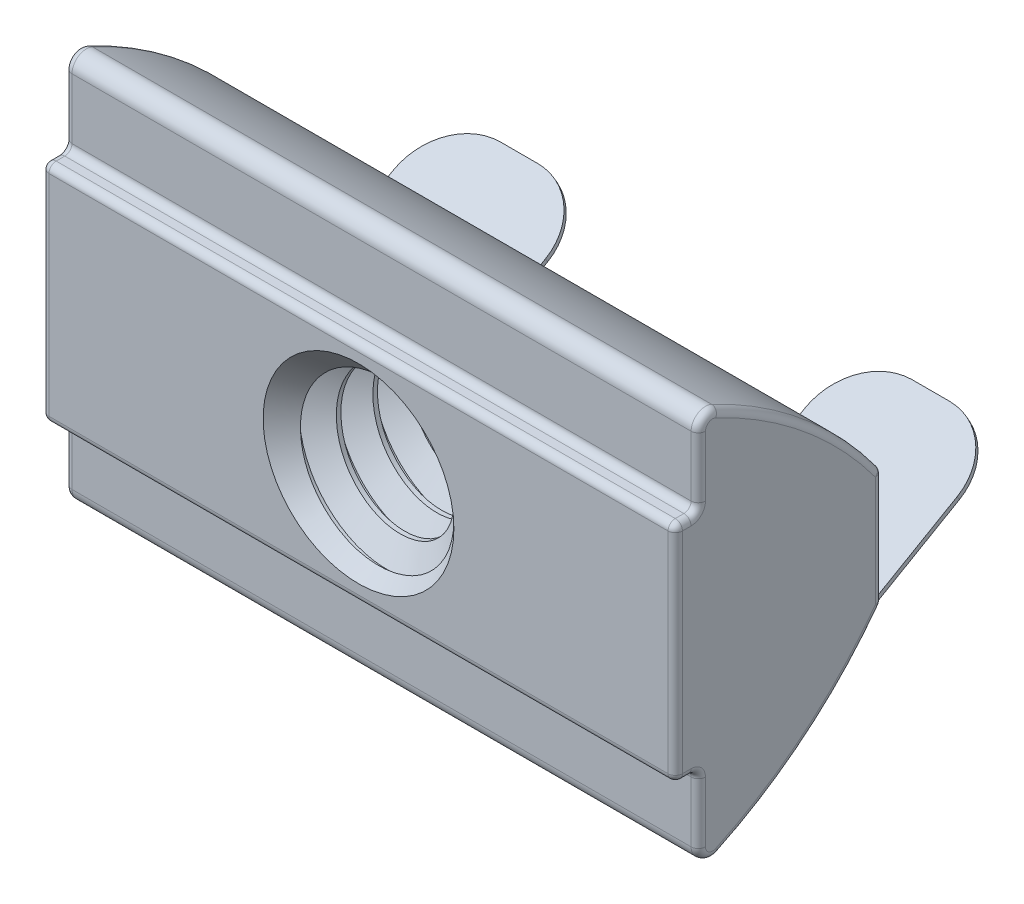
SolidWorks part; units mm, degrees
ref_plane "Front Plane" through (0, 0, 0) normal (0, 0, 1) x (1, 0, 0)
ref_plane "Top Plane" through (0, 0, 0) normal (0, 1, 0) x (1, 0, 0)
ref_plane "Right Plane" through (0, 0, 0) normal (1, 0, 0) x (0, 0, -1)
sketch "Sketch1" plane through (0, 0, 0) normal (0, 0, 1) x (1, 0, 0)
  line L1 (-11, 6.75) -> (11, 6.75)
  line L2 (-11, 6.75) -> (-11, -6.75)
  line L3 (-11, -6.75) -> (11, -6.75)
  line L4 (11, 6.75) -> (11, -6.75)
  circle A0 centre (0, 0) radius 3.175
  point P4 (0, 6.75)
  point P5 (0, 0)
  point P6 (-11, 0)
  point P11 (0, 3.175)
  dimension "Thread Diameter" = 6.35
  dimension "Length" = 22
  dimension "Width" = 13.5
sketch "Sketch2" plane through (0, 0, 0) normal (1, 0, 0) x (0, 0, -1)
  line L0 (-3.6, -3.9) -> (-3.6, 3.9)
  line L1 (-3.6, 3.9) -> (-2.8, 3.9)
  line L4 (-3.6, -3.9) -> (-2.8, -3.9)
  line L8 (-3.6, 0) -> (3.6, 0)
  line L13 (-4.7906, 3.3125) -> (-4.1556, 2.2126)
  line L14 (-4.1556, 2.2126) -> (-3.5206, 3.3125)
  line L15 (-3.5206, 3.3125) -> (-4.7906, 3.3125)
  line L16 (-4.1556, 3.3125) -> (-4.1556, 3.175)
  line L17 (-4.1556, 2.2126) -> (-4.1556, 2.3501)
  line L18 (-4.7113, 3.175) -> (-3.6, 3.175)
  line L19 (-4.7509, 3.2437) -> (-3.5603, 3.2437)
  line L20 (-4.235, 2.3501) -> (-4.0763, 2.3501)
  point P12 (0, 0)
  point P30 (9.2, 0)
  point P39 (-4.1556, 3.175)
  point P42 (-4.1556, 3.2437)
  point P45 (-4.1556, 2.3501)
  dimension "Thickness" = 7.2
  dimension "D2" = 7.8
  dimension "D3" = 0.8
  dimension "Thread Pitch" = 1.27
  dimension "D12" = 0.1588
  dimension "Spring Length" = 12
sketch "Sketch4" plane through (0, 0, 0) normal (1, 0, 0) x (0, 0, -1)
  line L3 (-3.6, -3.9) -> (-2.8, -3.9) construction
  line L4 (-3.6, -3.9) -> (-3.6, 3.9) construction
  line L5 (-3.6, 3.9) -> (-2.8, 3.9) construction
  line L11 (-3.6, -3.9) -> (-2.8, -3.9)
  line L12 (-3.6, -3.9) -> (-3.6, 3.9)
  line L13 (-3.6, 3.9) -> (-2.8, 3.9)
  line L16 (-2.8, 3.9) -> (-2.8, 6.25)
  line L17 (-2.8, -3.9) -> (-2.8, -6.25)
  line L18 (3.6, 2) -> (3.6, -2)
  arc A8 (-2.0859, 6.7019) -> (3.6, 2) centre (-8.5084, -6.8537) cw
  arc A9 (-2.0859, -6.7019) -> (3.6, -2) centre (-8.5084, 6.8537) ccw
  arc A10 (-2.0859, -6.7019) -> (-2.8, -6.25) centre (-2.3, -6.25) cw
  arc A11 (-2.0859, 6.7019) -> (-2.8, 6.25) centre (-2.3, 6.25) ccw
  point P14 (-2.3, 6.75)
  dimension "D1" = 0.5
  dimension "D2" = 15
  dimension "D3" = 4
extrude "Boss-Extrude1" add sketch "Sketch4" against normal up to vertex (11 mm away) and the other way up to vertex (11 mm away) up to point (-11, 6.75, 0) other way up to point (11, 6.75, 0)
sketch "Sketch6" plane through (0, 0, 3.6) normal (0, 0, 1) x (1, 0, 0)
  circle A0 centre (0, 0) radius 3.175 construction
  circle A1 centre (0, 0) radius 3.175
extrude "Cut-Extrude2" cut sketch "Sketch6" against normal through all
sketch "Sketch7" plane through (0, 0, 0) normal (1, 0, 0) x (0, 0, -1)
  line L8 (-2.0859, -6.7588) -> (9.125, -0.2862)
  line L9 (9.125, -0.2862) -> (9.2, -0.4161)
  line L10 (9.2, -0.4161) -> (-2.0109, -6.8887)
  line L11 (-2.0109, -6.8887) -> (-2.0859, -6.7588)
  line L12 (-2.8, -3.9) -> (-2.8, -6.25) construction
  arc A4 (-2.0859, -6.7019) -> (3.6, -2) centre (-8.5084, 6.8537) ccw construction
  arc A5 (-2.0859, -6.7019) -> (3.6, -2) centre (-8.5084, 6.8537) ccw construction
  dimension "D1" = 60
  dimension "D2" = 0.15
extrude "Boss-Extrude4" add sketch "Sketch7" along normal mid plane 19.6 separate body
sketch "Sketch8" plane through (0, -10.5492, 8.351) normal (0, 0.866, 0.5) x (1, 0, 0)
  line L6 (-4.5, 17.7662) -> (-4.5, 20.2662)
  line L7 (-4.5, 20.2662) -> (4.5, 20.2662)
  line L8 (4.5, 20.2662) -> (4.5, 17.7662)
  line L9 (0, 9.3891) -> (0, 15.6245) construction
  line L10 (9.8, 20.2662) -> (-9.8, 20.2662) construction
  arc A1 (-4.5, 17.7662) -> (4.5, 17.7662) centre (0, 17.7662) ccw
  dimension "D2" = 4.5
  dimension "D1" = 2.5
extrude "Cut-Extrude3" cut sketch "Sketch8" along normal through all
fillet "Fillet1" radius 2 4 edges at (-9.8, -0.3512, -9.1625) (-4.5, -0.3512, -9.1625) (4.5, -0.3512, -9.1625) (9.8, -0.3512, -9.1625)
sketch "Sketch17" plane through (0, -10.5492, 8.351) normal (0, 0.866, 0.5) x (1, 0, 0)
  line L0 (0, 9.3891) -> (0, 15.6245) construction
  line L3 (9.8, 7.3209) -> (-9.8, 7.3209) construction
  circle A0 centre (-7.7, 8.3209) radius 0.45
  circle A1 centre (0, 8.3209) radius 0.45
  circle A2 centre (7.7, 8.3209) radius 0.45
  dimension "D2" = 0.9
  dimension "D1" = 15.4
  dimension "D4" = 7.7
  dimension "D3" = 1
extrude "Boss-Extrude3" add sketch "Sketch17" against normal blind 0.075 draft 45
fillet "Fillet4" radius 0.125 6 edges at (7.7, -6.6412, 1.4322) (0, -6.6412, 1.4322) (-7.7, -6.6412, 1.4322) (7.7, -6.6137, 1.5346) (0, -6.6137, 1.5346) (-7.7, -6.6137, 1.5346)
fillet "Fillet5" radius 0.25 28 edges at (-11, 3.9, 3.2) (11, 3.9, 3.2) (-11, -3.9, 3.2) (11, -3.9, 3.2) (-11, 5.075, 2.8) (-11, 6.6725, 2.5674) (11, 5.075, 2.8) (11, 6.6725, 2.5674) (-11, -4.706, -1.0506) (-11, -6.6725, 2.5674) (11, -4.706, -1.0506) (11, -6.6725, 2.5674) (-11, 0, -3.6) (-11, 4.706, -1.0506) (-6.7329, 2, -3.6) (-6.7329, -2, -3.6) (6.7329, -2, -3.6) (6.7329, 2, -3.6) (11, 0, -3.6) (11, 4.706, -1.0506) (11, 0, 3.6) (-11, 0, 3.6) (-11, -5.075, 2.8) (11, -5.075, 2.8) (0, -3.9, 2.8) (0, -3.9, 3.6) (0, 3.9, 3.6) (0, 3.9, 2.8)
sketch "Sketch9" plane through (0, 0, 0) normal (0, 0, 1) x (1, 0, 0)
  line L0 (0, 0) -> (2.2451, -2.2451)
  line L2 (-11, 6.75) -> (11, 6.75) construction
  circle A0 centre (0, 0) radius 3.175 construction
  circle A1 centre (0, 0) radius 3.175
  point P0 (-11, 6.75)
  point P1 (11, 6.75)
  point P3 (-11, -6.75)
  point P13 (2.2451, -2.2451)
  dimension "D1" = 45
sketch "Sketch10" plane through (0, 0, 0) normal (1, 0, 0) x (0, 0, -1)
  point P0 (-3.6, 3.9)
  point P1 (3.6, 3.9)
  point P3 (9.2, 0)
  point P5 (-3.6, -3.9)
sketch "Sketch11" plane through (0, 0, 3.6) normal (0, 0, 1) x (1, 0, 0)
  circle A0 centre (0, 0) radius 3.175
curve "Helix/Spiral1" pitch 1.27 height 8.47 radius 3.175 centre (0, 0, 3.6) axis (0, 0, -1) start towards (0, 1, 0)
sketch "Sketch12" plane through (0, 0, 0) normal (1, 0, 0) x (0, 0, -1)
  line L0 (-4.235, 2.3501) -> (-4.0763, 2.3501) construction
  line L1 (-4.7906, 3.3125) -> (-4.1556, 2.2126) construction
  line L2 (-4.1556, 2.2126) -> (-3.5206, 3.3125) construction
  line L3 (-4.7509, 3.2437) -> (-3.5603, 3.2437) construction
  line L4 (-4.235, 2.3501) -> (-4.0763, 2.3501)
  line L5 (-4.7509, 3.2437) -> (-4.235, 2.3501)
  line L6 (-4.0763, 2.3501) -> (-3.5603, 3.2437)
  line L7 (-4.7509, 3.2437) -> (-3.5603, 3.2437)
sweep "Sweep1" add profiles "Sketch12" path "Helix/Spiral1"
sketch "Sketch13" plane through (0, 0, 3.6) normal (0, 0, 1) x (1, 0, 0)
  circle A0 centre (0, 0) radius 3.3125
extrude "Cut-Extrude4" cut sketch "Sketch13" against normal through all draft 45 and the other way through all
sketch "Sketch14" plane through (11, 0, 0) normal (1, 0, 0) x (0, 0, -1)
  line L6 (-2.8, -3.9) -> (-2.8, -6.25)
  line L7 (-2.8, -4.15) -> (-2.8, -6.25)
  line L8 (3.6, -2) -> (3.6, 2)
  line L9 (3.6, -1.918) -> (3.6, 1.918)
  line L10 (-2.8, 6.25) -> (-2.8, 3.9)
  line L11 (-2.8, 6.25) -> (-2.8, 4.15)
  line L12 (-2.8, 3.9) -> (-3.6, 3.9)
  line L13 (-3.6, 3.9) -> (-3.6, -3.9)
  line L14 (-3.6, -3.9) -> (-2.8, -3.9)
  line L20 (-3.05, 3.9) -> (-3.6, 3.9)
  line L21 (-3.6, 3.9) -> (-3.6, -3.9)
  line L22 (-3.6, -3.9) -> (-3.05, -3.9)
  arc A0 (3.551, -2.0666) -> (3.6, -1.918) centre (3.35, -1.918) ccw construction
  arc A1 (-2.8, -4.15) -> (-3.05, -3.9) centre (-3.05, -4.15) ccw construction
  arc A2 (-3.05, 3.9) -> (-2.8, 4.15) centre (-3.05, 4.15) ccw construction
  arc A3 (3.6, 1.918) -> (3.551, 2.0666) centre (3.35, 1.918) ccw construction
  arc A4 (-2.8, -6.25) -> (-2.0859, -6.7019) centre (-2.3, -6.25) ccw
  arc A5 (-2.8, -6.25) -> (-2.0859, -6.7019) centre (-2.3, -6.25) ccw
  arc A6 (-2.0859, -6.7019) -> (3.6, -2) centre (-8.5084, 6.8537) ccw
  arc A7 (-2.0859, -6.7019) -> (3.551, -2.0666) centre (-8.5084, 6.8537) ccw
  arc A12 (3.6, 2) -> (-2.0859, 6.7019) centre (-8.5084, -6.8537) ccw
  arc A13 (3.551, 2.0666) -> (-2.0859, 6.7019) centre (-8.5084, -6.8537) ccw
  arc A14 (-2.0859, 6.7019) -> (-2.8, 6.25) centre (-2.3, 6.25) ccw
  arc A15 (-2.0859, 6.7019) -> (-2.8, 6.25) centre (-2.3, 6.25) ccw
  arc A16 (3.551, -2.0666) -> (3.6, -1.918) centre (3.35, -1.918) ccw
  arc A17 (-2.8, -4.15) -> (-3.05, -3.9) centre (-3.05, -4.15) ccw
  arc A18 (-3.05, 3.9) -> (-2.8, 4.15) centre (-3.05, 4.15) ccw
  arc A19 (3.6, 1.918) -> (3.551, 2.0666) centre (3.35, 1.918) ccw
  dimension "D1" = 0
extrude "Cut-Extrude5" cut sketch "Sketch14" against normal through all flip side to cut
sketch "Sketch16" plane through (0, 0, 0) normal (1, 0, 0) x (0, 0, -1)
  line L0 (3.6, 0) -> (3.6, 4.1287)
  line L1 (3.6, 3.175) -> (2.6463, 3.175) construction
  line L2 (3.6, 4.1287) -> (0, 0.5287)
  line L3 (0, 0.5287) -> (0, 0)
  line L4 (0, 0) -> (3.6, 0)
  line L5 (-4.7113, 3.175) -> (-3.6, 3.175) construction
  arc A1 (3.6, 2) -> (-2.0859, 6.7019) centre (-8.5084, -6.8537) ccw construction
  dimension "D1" = 45
revolve "Cut-Revolve1" cut sketch "Sketch16" angle 360 about L4
equation "\"D12@Sketch2\"=\"Thread Pitch@Sketch2\"/8"
equation "\"D3@Helix/Spiral1\"=\"Thickness@Sketch2\"+\"Thread Pitch@Sketch2\""
equation "\"D4@Helix/Spiral1\"=\"Thread Pitch@Sketch2\""
equation "\"D4@Sketch17\"=\"D1@Sketch17\"/2"
equation "\"D1@Sketch17\"=\"Length@Sketch1\"*.7"
